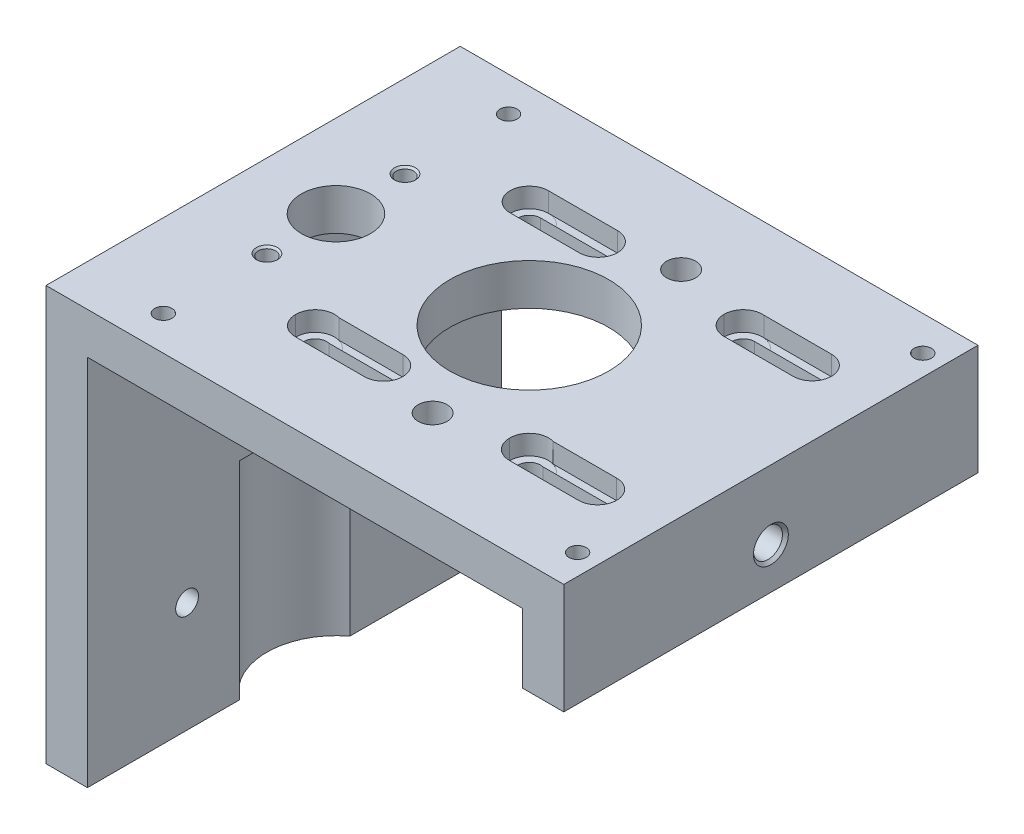
SolidWorks part; units mm, degrees
material "6061 Alloy"
ref_plane "Front Plane" through (0, 0, 0) normal (0, 0, 1) x (1, 0, 0)
ref_plane "Top Plane" through (0, 0, 0) normal (0, 1, 0) x (1, 0, 0)
ref_plane "Right Plane" through (0, 0, 0) normal (1, 0, 0) x (0, 0, -1)
sketch "Sketch1" plane through (0, 0, 0) normal (0, 0, 1) x (1, 0, 0)
  line L0 (0, 0) -> (6, 0)
  line L1 (69, 54) -> (69, 44)
  line L2 (0, 0) -> (0, 60)
  line L3 (0, 60) -> (75, 60)
  line L4 (75, 44) -> (75, 60)
  line L5 (69, 44) -> (75, 44)
  line L6 (6, 0) -> (6, 54)
  line L7 (6, 54) -> (69, 54)
  dimension "D1" = 75
  dimension "D2" = 6
  dimension "D3" = 6
  dimension "D4" = 60
  dimension "D5" = 10
  dimension "D6" = 6
extrude "Boss-Extrude1" add sketch "Sketch1" along normal blind 60
sketch "Sketch2" plane through (0, 60, 0) normal (0, 1, 0) x (1, 0, 0)
  line L0 (24.5, -45.5) -> (55.5, -45.5) construction
  line L1 (24.5, -45.5) -> (24.5, -14.5) construction
  line L3 (0, -60) -> (0, 0) construction
  line L4 (75, -30) -> (0, -30) construction
  line L5 (75, -60) -> (75, 0) construction
  circle A0 centre (40, -30) radius 11.5
  point P2 (24.5, -45.5)
  point P3 (40, -45.5)
  point P4 (24.5, -30)
  point P5 (55.5, -45.5)
  point P6 (24.5, -14.5)
  point P7 (55.5, -14.5)
  dimension "D1" = 23
  dimension "D2" = 31
  dimension "D3" = 31
  dimension "D7" = 40
  dimension "D4" = 2
  dimension "D5" = 2
extrude "Cut-Extrude1" cut sketch "Sketch2" against normal through all
ref_axis "Axis1" through (40, 54, 30) along (0, 1, 0)
hole_wizard "CBORE for #4 Socket Head Cap Screw1" positions "Sketch7" profile "Sketch6" counterbore size "#4" standard "Ansi Inch" end condition through all
sketch "Sketch7" plane through (0, 60, 0) normal (0, 1, 0) x (-1, 0, 0)
  line L0 (-24.5, 45.5) -> (-55.5, 45.5) construction
  line L1 (-24.5, 45.5) -> (-24.5, 14.5) construction
  point P0 (-24.5, 45.5)
  point P8 (-55.5, 45.5)
  point P9 (-24.5, 14.5)
  point P10 (-55.5, 14.5)
  point P34 (-40, 45.5)
  point P35 (-24.5, 30)
  point P36 (0, 0)
  point P37 (0, 0)
  dimension "D1" = 31
  dimension "D4" = 31
  dimension "D2" = 2
  dimension "D3" = 2
sketch "Sketch6" plane through (24.5, 60, 45.5) normal (1, 0, 0) x (0, 0, 1)
  line L0 (0, 0) -> (0, 60)
  line L1 (0, 60) -> (1.6319, 60)
  line L3 (1.6319, 60) -> (1.632, 2.8448)
  line L4 (1.632, 2.8448) -> (2.7788, 2.8448)
  line L5 (2.7788, 2.8448) -> (2.7788, 0)
  line L7 (2.7788, 0) -> (0, 0)
  line L11 (0, -6.35) -> (0, 107.95) construction
  dimension "Thru Hole Dia." = 3.2639
  dimension "Thru Hole Depth" = 60
  dimension "C'Bore Dia." = 5.5575
  dimension "C'Bore Depth" = 2.8448
sketch "Sketch24" plane through (0, 60, 0) normal (0, 1, 0) x (1, 0, 0)
  line L0 (24.5, -14.5) -> (34.5, -14.5) construction
  line L1 (24.5, -12.868) -> (34.5, -12.868)
  line L2 (24.5, -16.132) -> (34.5, -16.132)
  line L3 (65.5138, -30) -> (17.4578, -30) construction
  line L4 (55.5, -14.5) -> (65.5, -14.5) construction
  line L5 (55.5, -12.868) -> (65.5, -12.868)
  line L6 (55.5, -16.132) -> (65.5, -16.132)
  line L7 (24.5, -45.543) -> (34.5, -45.543) construction
  line L8 (24.5, -43.911) -> (34.5, -43.911)
  line L9 (24.5, -47.1749) -> (34.5, -47.1749)
  line L10 (55.5, -45.543) -> (65.5, -45.543) construction
  line L11 (55.5, -43.911) -> (65.5, -43.911)
  line L12 (55.5, -47.1749) -> (65.5, -47.1749)
  line L13 (40, -9.8721) -> (40, -50.1279) construction
  arc A0 (24.5, -12.868) -> (24.5, -16.132) centre (24.5, -14.5) ccw
  arc A1 (34.5, -16.132) -> (34.5, -12.868) centre (34.5, -14.5) ccw
  circle A2 centre (24.5, -14.5) radius 1.632 construction
  arc A3 (55.5, -12.868) -> (55.5, -16.132) centre (55.5, -14.5) ccw
  arc A4 (65.5, -16.132) -> (65.5, -12.868) centre (65.5, -14.5) ccw
  arc A5 (24.5, -43.911) -> (24.5, -47.1749) centre (24.5, -45.543) ccw
  arc A6 (34.5, -47.1749) -> (34.5, -43.911) centre (34.5, -45.543) ccw
  arc A7 (55.5, -43.911) -> (55.5, -47.1749) centre (55.5, -45.543) ccw
  arc A8 (65.5, -47.1749) -> (65.5, -43.911) centre (65.5, -45.543) ccw
  point P3 (29.5, -14.5)
  point P18 (60.5, -14.5)
  point P25 (29.5, -45.543)
  point P32 (60.5, -45.543)
  dimension "D1" = 10
  dimension "D2" = 2
  dimension "D3" = 2
extrude "Cut-Extrude5" cut sketch "Sketch24" against normal up to next
sketch "Sketch25" plane through (0, 60, 0) normal (0, 1, 0) x (1, 0, 0)
  line L0 (24.5, -14.5) -> (34.5, -14.5) construction
  line L1 (24.5, -11.7212) -> (34.5, -11.7212)
  line L2 (24.5, -17.2788) -> (34.5, -17.2788)
  line L3 (55.5, -14.5099) -> (65.5, -14.5099) construction
  line L4 (55.5, -11.7311) -> (65.5, -11.7311)
  line L5 (55.5, -17.2886) -> (65.5, -17.2886)
  line L6 (24.5, -45.6008) -> (34.5, -45.6008) construction
  line L7 (24.5, -42.8221) -> (34.5, -42.8221)
  line L8 (24.5, -48.3796) -> (34.5, -48.3796)
  line L9 (55.5, -45.6107) -> (65.5, -45.6107) construction
  line L10 (55.5, -42.832) -> (65.5, -42.832)
  line L11 (55.5, -48.3895) -> (65.5, -48.3895)
  arc A0 (24.5, -11.7212) -> (24.5, -17.2788) centre (24.5, -14.5) ccw
  arc A1 (34.5, -17.2788) -> (34.5, -11.7212) centre (34.5, -14.5) ccw
  arc A2 (26.7491, -12.868) -> (26.7491, -16.132) centre (24.5, -14.5) ccw construction
  arc A3 (55.5, -11.7311) -> (55.5, -17.2886) centre (55.5, -14.5099) ccw
  arc A4 (65.5, -17.2886) -> (65.5, -11.7311) centre (65.5, -14.5099) ccw
  arc A5 (24.5, -42.8221) -> (24.5, -48.3796) centre (24.5, -45.6008) ccw
  arc A6 (34.5, -48.3796) -> (34.5, -42.8221) centre (34.5, -45.6008) ccw
  arc A7 (55.5, -42.832) -> (55.5, -48.3895) centre (55.5, -45.6107) ccw
  arc A8 (65.5, -48.3895) -> (65.5, -42.832) centre (65.5, -45.6107) ccw
  point P4 (29.5, -14.5)
  point P17 (60.5, -14.5099)
  point P24 (29.5, -45.6008)
  point P31 (60.5, -45.6107)
  dimension "D1" = 10
  dimension "D2" = 2
  dimension "D3" = 2
extrude "Cut-Extrude6" cut sketch "Sketch25" against normal blind 2.84
hole_wizard "M3 Tapped Hole1" positions "Sketch9" profile "Sketch10" tap size "M3" standard "ISO"
sketch "Sketch9" plane through (0, 60, 0) normal (0, 1, 0) x (-1, 0, 0)
  line L0 (-12, 55) -> (-72, 55) construction
  line L1 (-12, 55) -> (-12, 5) construction
  line L20 (-75, 60) -> (0, 60) construction
  line L21 (0, 60) -> (0, 0) construction
  point P1 (-12, 55)
  point P5 (-72, 55)
  point P6 (-12, 5)
  point P7 (-72, 5)
  dimension "D1" = 60
  dimension "D2" = 50
  dimension "D6" = 5
  dimension "D7" = 12
  dimension "D3" = 2
  dimension "D4" = 2
sketch "Sketch10" plane through (12, 60, 55) normal (1, 0, 0) x (0, 0, 1)
  line L0 (0, 0) -> (0, 9.2511)
  line L1 (0, 9.2511) -> (1.25, 8.5)
  line L2 (1.25, 8.5) -> (1.25, 0)
  line L5 (1.25, 0) -> (0, 0)
  line L10 (0, 9.2511) -> (-1.25, 8.5) construction
  line L11 (0, -6.35) -> (0, 107.95) construction
  dimension "Tap Drill Dia." = 2.5
  dimension "Tap Drill Depth" = 8.5
  dimension "Drill Angle" = 118
cosmetic thread "Hole Thread1" parameters "D1"=6, "D2"=3
cosmetic thread "Hole Thread2" parameters "D1"=6, "D2"=3
cosmetic thread "Hole Thread3" parameters "D1"=6, "D2"=3
cosmetic thread "Hole Thread4" parameters "D1"=6, "D2"=3
hole_wizard "M5 Tapped Hole1" positions "Sketch14" profile "Sketch15" tap size "M5" standard "ISO" end condition through all
sketch "Sketch14" plane through (0, 60, 0) normal (0, 1, 0) x (-1, 0, 0)
  line L0 (-44, 12) -> (-44, 48) construction
  point P0 (-44, 12)
  point P1 (-44, 48)
  dimension "D1" = 18
  dimension "D2" = 18
  dimension "D3" = 4
sketch "Sketch15" plane through (44, 60, 12) normal (1, 0, 0) x (0, 0, 1)
  line L0 (0, 0) -> (0, 60)
  line L1 (0, 60) -> (2.1, 60)
  line L2 (2.1, 60) -> (2.1, 0)
  line L5 (2.1, 0) -> (0, 0)
  line L11 (0, -6.35) -> (0, 107.95) construction
  dimension "Thru Tap Drill Dia." = 4.2
  dimension "Thru Tap Drill Depth" = 60
cosmetic thread "Hole Thread5" parameters "D2"=5
cosmetic thread "Hole Thread6" parameters "D2"=5
sketch "Sketch11" plane through (0, 60, 0) normal (0, 1, 0) x (1, 0, 0)
  line L1 (0, -60) -> (0, 0) construction
  line L2 (75, -30) -> (0, -30) construction
  line L3 (75, -60) -> (75, 0) construction
  circle A0 centre (12, -30) radius 5
  dimension "D2" = 10
  dimension "D1" = 12
extrude "Cut-Extrude2" cut sketch "Sketch11" against normal through all
ref_axis "Axis2" through (12, 54, 30) along (0, 1, 0)
hole_wizard "M4 Tapped Hole1" positions "Sketch20" profile "Sketch19" tap size "M4" standard "ISO" end condition up to next
sketch "Sketch20" plane through (0, 0, 0) normal (-1, 0, 0) x (0, 0, 1)
  line L0 (30, 60) -> (30, 0) construction
  line L1 (60, 60) -> (0, 60) construction
  line L2 (60, 0) -> (0, 0) construction
  point P0 (11, 46)
  point P13 (11, 16)
  point P16 (49, 46)
  point P18 (45.5672, 16)
  dimension "D1" = 14
  dimension "D2" = 30
  dimension "D3" = 38
cosmetic thread "Hole Thread7" parameters "D2"=4
cosmetic thread "Hole Thread8" parameters "D2"=4
cosmetic thread "Hole Thread9" parameters "D2"=4
cosmetic thread "Hole Thread10" parameters "D2"=4
sketch "Sketch19" plane through (0, 46, 11) normal (0, 1, 0) x (0, 0, 1)
  line L0 (0, 0) -> (0, 6)
  line L1 (0, 6) -> (1.65, 6)
  line L2 (1.65, 6) -> (1.65, 0.6)
  line L3 (1.65, 0.6) -> (2.25, 0)
  line L5 (2.25, 0) -> (0, 0)
  line L6 (-1.65, 0.6) -> (-2.25, 0) construction
  line L11 (0, -6.35) -> (0, 107.95) construction
  dimension "Thru Tap Drill Dia." = 3.3
  dimension "Thru Tap Drill Depth" = 6
  dimension "Near C'Sink Dia." = 4.5
  dimension "Near C'Sink Angle" = 90
hole_wizard "M5 Tapped Hole2" positions "Sketch23" profile "Sketch22" tap size "M5" standard "ISO" end condition up to next
sketch "Sketch23" plane through (75, 0, 0) normal (1, 0, 0) x (0, 0, -1)
  line L0 (-30, 54) -> (-30, 60) construction
  line L1 (-60, 60) -> (0, 60) construction
  point P0 (-30, 50)
  dimension "D1" = 10
cosmetic thread "Hole Thread11" parameters "D2"=5
sketch "Sketch22" plane through (75, 50, 30) normal (0, 1, 0) x (0, 0, -1)
  line L0 (0, 0) -> (0, 6)
  line L1 (0, 6) -> (2.1, 6)
  line L2 (2.1, 6) -> (2.1, 0.425)
  line L3 (2.1, 0.425) -> (2.525, 0)
  line L5 (2.525, 0) -> (0, 0)
  line L6 (-2.1, 0.425) -> (-2.525, 0) construction
  line L11 (0, -6.35) -> (0, 107.95) construction
  dimension "Thru Tap Drill Dia." = 4.2
  dimension "Thru Tap Drill Depth" = 6
  dimension "Near C'Sink Dia." = 5.05
  dimension "Near C'Sink Angle" = 90
sketch "Sketch16" plane through (0, 0, 0) normal (0, -1, 0) x (1, 0, 0)
  circle A0 centre (12, 30) radius 10
extrude "Cut-Extrude4" cut sketch "Sketch16" against normal blind 30
hole_wizard "M3 Tapped Hole2" positions "Sketch28" profile "Sketch29" tap size "M3" standard "ISO" end condition up to next
sketch "Sketch28" plane through (0, 54, 0) normal (0, -1, 0) x (1, 0, 0)
  line L0 (12, 43.3514) -> (12, 16.6486) construction
  line L2 (20.0951, 30) -> (3.9049, 30) construction
  point P12 (12, 40)
  point P26 (12, 20)
  dimension "D1" = 20
cosmetic thread "Hole Thread12" parameters "D2"=3
cosmetic thread "Hole Thread13" parameters "D2"=3
sketch "Sketch29" plane through (12, 54, 40) normal (1, 0, 0) x (0, 0, -1)
  line L0 (0, 0) -> (0, 6)
  line L1 (0, 6) -> (1.525, 6)
  line L2 (1.25, 5.725) -> (1.25, 0.275)
  line L3 (1.25, 0.275) -> (1.525, 0)
  line L5 (1.525, 0) -> (0, 0)
  line L6 (-1.25, 0.275) -> (-1.525, 0) construction
  line L7 (1.525, 6) -> (1.25, 5.725)
  line L8 (-1.525, 6) -> (-1.25, 5.725) construction
  line L11 (0, -6.35) -> (0, 107.95) construction
  dimension "Thru Tap Drill Dia." = 2.5
  dimension "Thru Tap Drill Depth" = 6
  dimension "Near C'Sink Dia." = 3.05
  dimension "Near C'Sink Angle" = 90
  dimension "Far C'Sink Dia." = 3.05
  dimension "Far C'Sink Angle" = 90
